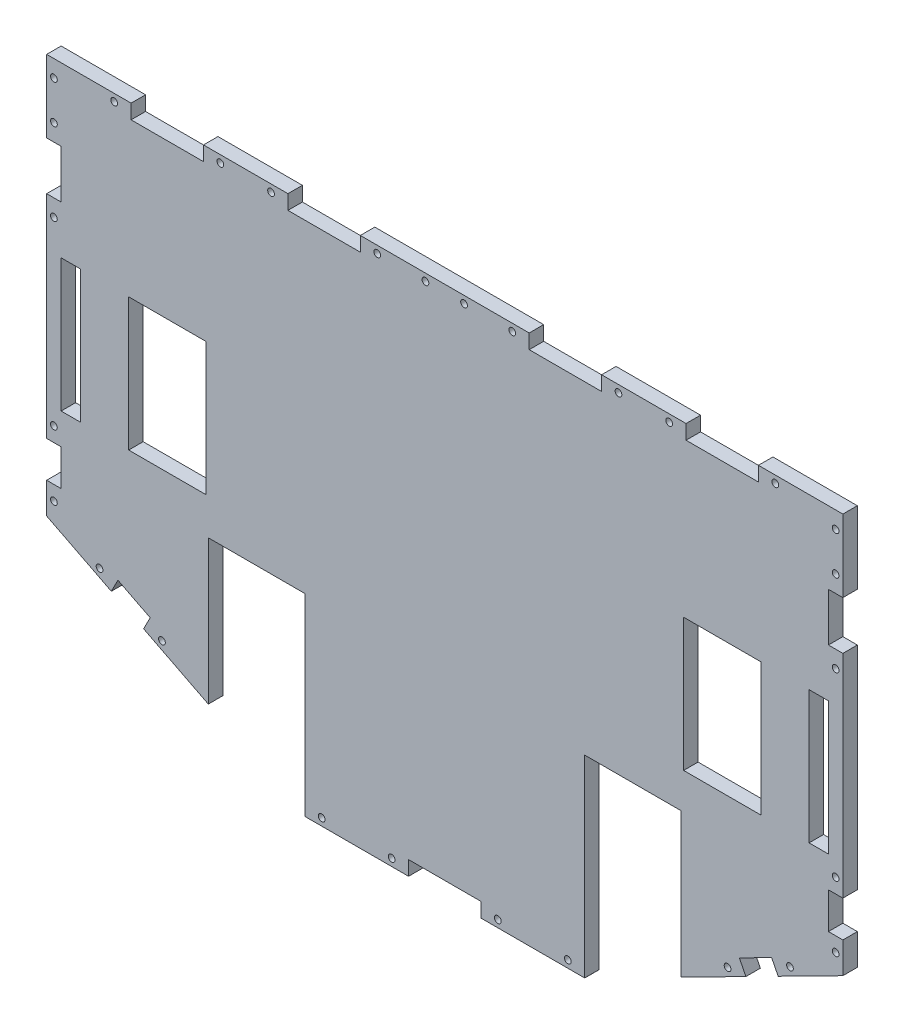
SolidWorks part; units mm, degrees
ref_plane "Plan de face" through (0, 0, 0) normal (0, 0, 1) x (1, 0, 0)
ref_plane "Plan de dessus" through (0, 0, 0) normal (0, 1, 0) x (1, 0, 0)
ref_plane "Plan de droite" through (0, 0, 0) normal (1, 0, 0) x (0, 0, -1)
sketch "Esquisse1" plane through (0, 0, 0) normal (0, 0, 1) x (1, 0, 0)
  line L0 (0, 124.9429) -> (0, -204.46) construction
  line L1 (-165, 110.0116) -> (165, 110.0116)
  line L2 (165, 110.0116) -> (165, -55.6884)
  line L3 (165, -55.6884) -> (58, -110.0116)
  line L4 (58, -110.0116) -> (-58, -110.0116)
  line L5 (-211.9802, 0) -> (248.5953, 0) construction
  line L6 (-58, -110.0116) -> (-165, -55.6884)
  line L7 (-165, -55.6884) -> (-165, 110.0116)
  dimension "D1" = 330
  dimension "D2" = 165
  dimension "D3" = 165.7
  dimension "D4" = 165.7
  dimension "D5" = 120
  dimension "D6" = 120
  dimension "D7" = 116
  dimension "D8" = 220.0231
  dimension "D9" = 110.0116
extrude "Boss.-Extru.1" add sketch "Esquisse1" along normal blind 6
sketch "Esquisse2" plane through (0, 0, 6) normal (0, 0, 1) x (1, 0, 0)
  line L1 (-159, 39.9884) -> (-151, 39.9884)
  line L2 (-159, 39.9884) -> (-159, -15.0116)
  line L3 (-159, -15.0116) -> (-151, -15.0116)
  line L4 (-151, 39.9884) -> (-151, -15.0116)
  line L5 (-131, 39.9884) -> (-99, 39.9884)
  line L6 (-131, 39.9884) -> (-131, -15.0116)
  line L7 (-131, -15.0116) -> (-99, -15.0116)
  line L8 (-99, 39.9884) -> (-99, -15.0116)
  line L9 (0, 145.0258) -> (0, -189.2208) construction
  line L10 (99, 39.9884) -> (99, -15.0116)
  line L11 (131, -15.0116) -> (99, -15.0116)
  line L12 (131, 39.9884) -> (131, -15.0116)
  line L13 (131, 39.9884) -> (99, 39.9884)
  line L14 (151, 39.9884) -> (151, -15.0116)
  line L15 (159, -15.0116) -> (151, -15.0116)
  line L16 (159, 39.9884) -> (159, -15.0116)
  line L17 (159, 39.9884) -> (151, 39.9884)
  line L19 (98, -110) -> (98, -30)
  line L20 (-58, -110) -> (-98, -110)
  line L21 (-58, -110) -> (-58, -30)
  line L22 (-58, -30) -> (-98, -30)
  line L23 (-98, -110) -> (-98, -30)
  line L24 (58, -30) -> (98, -30)
  line L25 (58, -110) -> (58, -30)
  line L26 (58, -110) -> (98, -110)
  line L27 (-165, 110.0116) -> (-165, -55.6884) construction
  line L28 (-58, -110.0116) -> (58, -110.0116) construction
  dimension "D2" = 8
  dimension "D3" = 20
  dimension "D4" = 32
  dimension "D5" = 99
  dimension "D6" = 55
  dimension "D7" = 55
  dimension "D8" = 95
  dimension "D9" = 95
  dimension "D10" = 40
  dimension "D11" = 80
  dimension "D12" = 67
  dimension "D13" = 116
  dimension "D14" = 6
extrude "Enlèv. mat.-Extru.1" cut sketch "Esquisse2" against normal blind 6
sketch "Esquisse8" plane through (0, 0, 6) normal (0, 0, 1) x (1, 0, 0)
  line L0 (-165, 110.0116) -> (-165, -55.6884) construction
  line L1 (-165, -42.8484) -> (-159, -42.8484)
  line L2 (-165, -42.8484) -> (-165, -27.8484)
  line L3 (-165, -27.8484) -> (-159, -27.8484)
  line L4 (-159, -42.8484) -> (-159, -27.8484)
  line L5 (165, 110.0116) -> (-165, 110.0116) construction
  line L6 (-165, 60.0116) -> (-159, 60.0116)
  line L7 (-165, 60.0116) -> (-165, 80.0116)
  line L8 (-165, 80.0116) -> (-159, 80.0116)
  line L9 (-159, 60.0116) -> (-159, 80.0116)
  line L10 (-130, 110.0116) -> (-100, 110.0116)
  line L11 (-130, 110.0116) -> (-130, 104.0116)
  line L12 (-130, 104.0116) -> (-100, 104.0116)
  line L13 (-100, 110.0116) -> (-100, 104.0116)
  line L14 (0, 123.4485) -> (0, -147.0642) construction
  line L15 (-65, 110.0116) -> (-35, 110.0116)
  line L16 (-65, 110.0116) -> (-65, 104.0116)
  line L17 (-65, 104.0116) -> (-35, 104.0116)
  line L18 (-35, 110.0116) -> (-35, 104.0116)
  line L19 (159, -42.8484) -> (159, -27.8484)
  line L20 (165, -27.8484) -> (159, -27.8484)
  line L21 (165, -42.8484) -> (165, -27.8484)
  line L22 (165, -42.8484) -> (159, -42.8484)
  line L23 (35, 110.0116) -> (35, 104.0116)
  line L24 (65, 104.0116) -> (35, 104.0116)
  line L25 (65, 110.0116) -> (65, 104.0116)
  line L26 (65, 110.0116) -> (35, 110.0116)
  line L27 (100, 110.0116) -> (100, 104.0116)
  line L28 (130, 104.0116) -> (100, 104.0116)
  line L29 (130, 110.0116) -> (130, 104.0116)
  line L30 (130, 110.0116) -> (100, 110.0116)
  line L31 (159, 60.0116) -> (159, 80.0116)
  line L32 (165, 80.0116) -> (159, 80.0116)
  line L33 (165, 60.0116) -> (165, 80.0116)
  line L34 (165, 60.0116) -> (159, 60.0116)
  line L35 (-58, -110.0116) -> (58, -110.0116) construction
  line L36 (-15, -110.0116) -> (15, -110.0116)
  line L37 (-15, -110.0116) -> (-15, -104.0116)
  line L38 (-15, -104.0116) -> (15, -104.0116)
  line L39 (15, -110.0116) -> (15, -104.0116)
  line L40 (-58, -110) -> (-58, -30) construction
  line L41 (-138.1876, -69.3009) -> (-124.8126, -76.0913)
  line L42 (-138.1876, -69.3009) -> (-135.4714, -63.9509)
  line L43 (-124.8126, -76.0913) -> (-122.0964, -70.7413)
  line L44 (-135.4714, -63.9509) -> (-122.0964, -70.7413)
  line L45 (-165, -55.6884) -> (-98, -89.7039) construction
  line L46 (135.4714, -63.9509) -> (122.0964, -70.7413)
  line L47 (124.8126, -76.0913) -> (122.0964, -70.7413)
  line L48 (138.1876, -69.3009) -> (135.4714, -63.9509)
  line L49 (138.1876, -69.3009) -> (124.8126, -76.0913)
  dimension "D1" = 6
  dimension "D2" = 15
  dimension "D3" = 12.84
  dimension "D4" = 6
  dimension "D5" = 6
  dimension "D6" = 20
  dimension "D7" = 30
  dimension "D8" = 30
  dimension "D9" = 6
  dimension "D10" = 35
  dimension "D11" = 35
  dimension "D12" = 30
  dimension "D13" = 30
  dimension "D14" = 6
  dimension "D15" = 43
  dimension "D16" = 6
  dimension "D17" = 15
  dimension "D18" = 30.07
  dimension "D19" = 30.0702
extrude "Enlèv. mat.-Extru.2" cut sketch "Esquisse8" against normal blind 6
sketch "Esquisse9" plane through (0, 0, 6) normal (0, 0, 1) x (1, 0, 0)
  line L0 (0, 149.6894) -> (0, -144.2465) construction
  line L1 (35, 110.0116) -> (-35, 110.0116) construction
  line L2 (-65, 110.0116) -> (-100, 110.0116) construction
  line L3 (-35, 104.0116) -> (-35, 110.0116) construction
  line L4 (-65, 110.0116) -> (-65, 104.0116) construction
  line L5 (-100, 104.0116) -> (-100, 110.0116) construction
  line L6 (-130, 110.0116) -> (-130, 104.0116) construction
  line L7 (-130, 110.0116) -> (-165, 110.0116) construction
  line L8 (-165, 110.0116) -> (-165, 80.0116) construction
  line L9 (-159, 80.0116) -> (-165, 80.0116) construction
  line L10 (-165, 60.0116) -> (-159, 60.0116) construction
  line L11 (-165, 60.0116) -> (-165, -27.8484) construction
  line L12 (-159, -27.8484) -> (-165, -27.8484) construction
  line L13 (-165, -42.8484) -> (-165, -55.6884) construction
  line L14 (-165, -42.8484) -> (-159, -42.8484) construction
  line L15 (-58, -110.0116) -> (-15, -110.0116) construction
  line L16 (-15, -104.0116) -> (-15, -110.0116) construction
  line L17 (-58, -110) -> (-58, -30) construction
  line L18 (-124.8126, -76.0913) -> (-122.0964, -70.7413) construction
  line L19 (-135.4714, -63.9509) -> (-138.1876, -69.3009) construction
  line L20 (-165, -55.6884) -> (-138.1876, -69.3009) construction
  line L21 (-124.8126, -76.0913) -> (-98, -89.7039) construction
  circle A0 centre (-162, -48.8484) radius 1.4
  circle A1 centre (-162, -21.8484) radius 1.4
  circle A2 centre (-162, 53.0116) radius 1.4
  circle A3 centre (-162, 87.0116) radius 1.4
  circle A4 centre (-162, 103.0116) radius 1.4
  circle A5 centre (-137, 107.0116) radius 1.4
  circle A6 centre (-93, 107.0116) radius 1.4
  circle A7 centre (-72, 107.0116) radius 1.4
  circle A8 centre (-28, 107.0116) radius 1.4
  circle A9 centre (-8, 107.0116) radius 1.4
  circle A10 centre (8, 107.0116) radius 1.4
  circle A11 centre (28, 107.0116) radius 1.4
  circle A12 centre (72, 107.0116) radius 1.4
  circle A13 centre (93, 107.0116) radius 1.4
  circle A14 centre (137, 107.0116) radius 1.4
  circle A15 centre (162, 103.0116) radius 1.4
  circle A16 centre (162, 87.0116) radius 1.4
  circle A17 centre (162, 53.0116) radius 1.4
  circle A18 centre (162, -21.8484) radius 1.4
  circle A19 centre (162, -48.8484) radius 1.4
  circle A20 centre (-51, -107.0116) radius 1.4
  circle A21 centre (-22, -107.0116) radius 1.4
  circle A22 centre (22, -107.0116) radius 1.4
  circle A23 centre (51, -107.0116) radius 1.4
  circle A24 centre (-143.0712, -63.4571) radius 1.4
  circle A25 centre (-117.2128, -76.5851) radius 1.4
  circle A26 centre (117.2128, -76.5851) radius 1.4
  circle A27 centre (143.0712, -63.4571) radius 1.4
  point P29 (-65, 107.0116)
  point P42 (-162, 60.0116)
  point P93 (-136.8295, -66.6259)
  dimension "D1" = 2.8
  dimension "D2" = 2.8
  dimension "D3" = 2.8
  dimension "D4" = 3
  dimension "D5" = 3
  dimension "D7" = 2.8
  dimension "D8" = 20
  dimension "D9" = 3
  dimension "D10" = 7
  dimension "D11" = 7
  dimension "D12" = 3
  dimension "D13" = 2.8
  dimension "D14" = 7
  dimension "D15" = 3
  dimension "D16" = 7
  dimension "D17" = 2.8
  dimension "D18" = 3
  dimension "D19" = 3
  dimension "D20" = 7
  dimension "D21" = 2.8
  dimension "D22" = 2.8
  dimension "D23" = 7
  dimension "D24" = 3
  dimension "D25" = 2.8
  dimension "D26" = 3
  dimension "D27" = 6
  dimension "D28" = 2.8
  dimension "D29" = 3
  dimension "D30" = 6
  dimension "D31" = 2.8
  dimension "D32" = 2.8
  dimension "D33" = 3
  dimension "D34" = 3
  dimension "D35" = 7
  dimension "D36" = 7
  dimension "D37" = 2.8
  dimension "D38" = 2.8
  dimension "D39" = 7
  dimension "D40" = 7
  dimension "D41" = 3
  dimension "D42" = 3
  dimension "D6" = 7
extrude "Enlèv. mat.-Extru.3" cut sketch "Esquisse9" against normal blind 6
equation "\"D2@Esquisse1\"=\"D1@Esquisse1\"/2"
equation "\"D9@Esquisse1\"=\"D8@Esquisse1\"/2"
